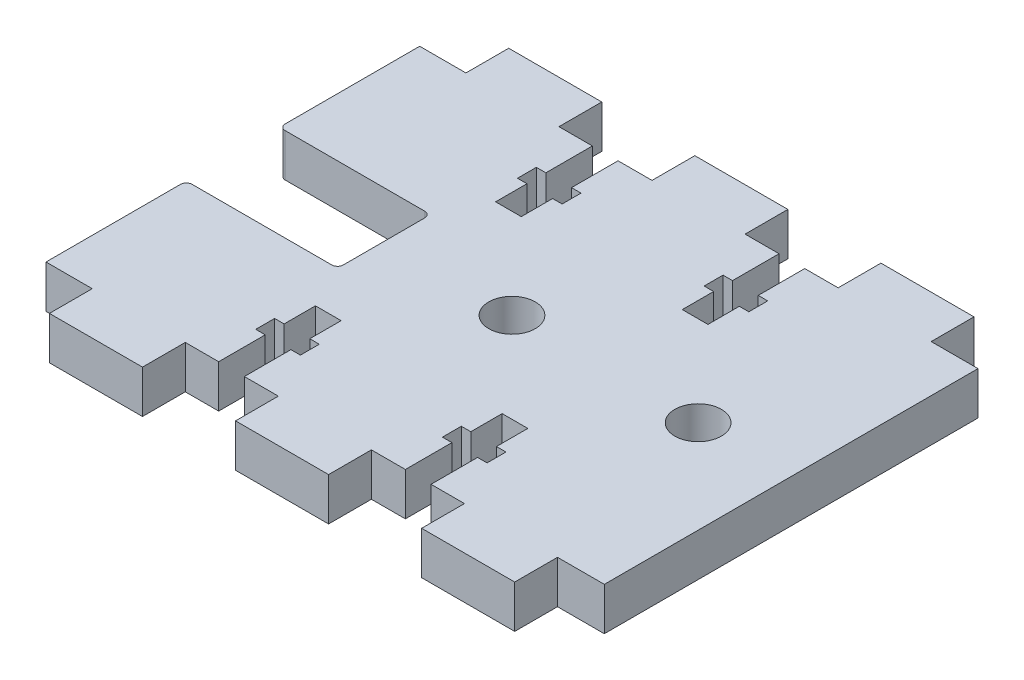
SolidWorks part; units mm, degrees
ref_plane "Front Plane" through (0, 0, 0) normal (0, 0, 1) x (1, 0, 0)
ref_plane "Top Plane" through (0, 0, 0) normal (0, 1, 0) x (1, 0, 0)
ref_plane "Right Plane" through (0, 0, 0) normal (1, 0, 0) x (0, 0, -1)
sketch "Sketch1" plane through (0, 0, 0) normal (0, 1, 0) x (1, 0, 0)
  line L0 (38.1, 0) -> (-38.1, 0) construction
  line L1 (38.1, -25.5) -> (31.7104, -25.5)
  line L2 (38.1, -25.5) -> (38.1, 25.5)
  line L3 (38.1, 25.5) -> (31.7104, 25.5)
  line L4 (-38.1, -25.5) -> (-38.1, 25.5)
  line L5 (38.1, -25.5) -> (-38.1, 25.5) construction
  line L6 (38.1, 25.5) -> (-38.1, -25.5) construction
  line L7 (-0.0396, 25.3) -> (-0.0396, -25.7) construction
  line L8 (-6.3896, 25.5) -> (-11.0266, 25.5)
  line L9 (6.3104, 31.342) -> (-6.3896, 31.342)
  line L10 (6.3104, 31.342) -> (6.3104, 25.5)
  line L11 (-31.7896, 25.5) -> (-38.1, 25.5)
  line L12 (-6.3896, 31.342) -> (-6.3896, 25.5)
  line L13 (6.3104, 31.342) -> (-6.3896, 25.5) construction
  line L14 (6.3104, 25.5) -> (-6.3896, 31.342) construction
  line L15 (31.7104, 31.342) -> (19.0104, 25.5) construction
  line L16 (-31.7896, 25.5) -> (-31.7896, 31.342)
  line L17 (-31.7896, 31.342) -> (-19.0896, 31.342)
  line L18 (-19.0896, 25.5) -> (-19.0896, 31.342)
  line L19 (-31.7896, 25.5) -> (-19.0896, 31.342) construction
  line L20 (-31.7896, 31.342) -> (-19.0896, 25.5) construction
  line L21 (31.7104, 25.5) -> (19.0104, 31.342) construction
  line L22 (19.0104, 25.5) -> (19.0104, 31.342)
  line L23 (31.7104, 31.342) -> (19.0104, 31.342)
  line L24 (31.7104, 25.5) -> (31.7104, 31.342)
  line L25 (19.0104, 25.5) -> (14.4526, 25.5)
  line L26 (-12.7792, 25.1) -> (-12.7792, 0) construction
  line L27 (12.7, 25.5) -> (12.7, -25.5) construction
  line L28 (-9.7312, 16.5719) -> (-9.7312, 19.15)
  line L29 (-14.5318, 16.5719) -> (-15.8272, 16.5719)
  line L30 (-11.0266, 19.15) -> (-11.0266, 25.5)
  line L31 (10.9474, 16.5719) -> (14.4526, 12.292) construction
  line L32 (-14.5318, 19.15) -> (-14.5318, 25.5)
  line L33 (-11.0266, 19.15) -> (-14.5318, 25.5) construction
  line L34 (-11.0266, 25.5) -> (-14.5318, 19.15) construction
  line L35 (-9.7312, 16.5719) -> (-11.0266, 16.5719)
  line L36 (-15.8272, 16.5719) -> (-15.8272, 19.15)
  line L37 (-9.7312, 19.15) -> (-11.0266, 19.15)
  line L38 (-14.5318, 19.15) -> (-15.8272, 19.15)
  line L39 (-14.5318, 25.5) -> (-19.0896, 25.5)
  line L40 (10.9474, 12.292) -> (14.4526, 16.5719) construction
  line L41 (-11.0266, 12.292) -> (-14.5318, 12.292)
  line L42 (-11.0266, 12.292) -> (-11.0266, 16.5719)
  line L43 (10.9474, 25.5) -> (14.4526, 19.15) construction
  line L44 (-14.5318, 12.292) -> (-14.5318, 16.5719)
  line L45 (-11.0266, 12.292) -> (-14.5318, 16.5719) construction
  line L46 (-11.0266, 16.5719) -> (-14.5318, 12.292) construction
  line L47 (10.9474, 19.15) -> (14.4526, 25.5) construction
  line L48 (14.4526, 12.292) -> (14.4526, 16.5719)
  line L49 (10.9474, 12.292) -> (10.9474, 16.5719)
  line L50 (10.9474, 12.292) -> (14.4526, 12.292)
  line L51 (14.4526, 19.15) -> (15.748, 19.15)
  line L52 (9.652, 19.15) -> (10.9474, 19.15)
  line L53 (15.748, 16.5719) -> (15.748, 19.15)
  line L54 (9.652, 16.5719) -> (10.9474, 16.5719)
  line L55 (14.4526, 19.15) -> (14.4526, 25.5)
  line L56 (10.9474, 19.15) -> (10.9474, 25.5)
  line L57 (14.4526, 16.5719) -> (15.748, 16.5719)
  line L58 (9.652, 16.5719) -> (9.652, 19.15)
  line L59 (10.9474, 25.5) -> (6.3104, 25.5)
  line L60 (10.9474, -19.15) -> (14.4526, -25.5) construction
  line L61 (10.9474, -25.5) -> (14.4526, -19.15) construction
  line L62 (10.9474, -12.292) -> (14.4526, -16.5719) construction
  line L63 (10.9474, -16.5719) -> (14.4526, -12.292) construction
  line L64 (9.652, -16.5719) -> (9.652, -19.15)
  line L65 (14.4526, -16.5719) -> (15.748, -16.5719)
  line L66 (10.9474, -19.15) -> (10.9474, -25.5)
  line L67 (14.4526, -19.15) -> (14.4526, -25.5)
  line L68 (9.652, -16.5719) -> (10.9474, -16.5719)
  line L69 (15.748, -16.5719) -> (15.748, -19.15)
  line L70 (9.652, -19.15) -> (10.9474, -19.15)
  line L71 (14.4526, -19.15) -> (15.748, -19.15)
  line L72 (10.9474, -12.292) -> (14.4526, -12.292)
  line L73 (10.9474, -12.292) -> (10.9474, -16.5719)
  line L74 (14.4526, -12.292) -> (14.4526, -16.5719)
  line L75 (-14.5318, -16.5719) -> (-15.8272, -16.5719)
  line L76 (-14.5318, -19.15) -> (-15.8272, -19.15)
  line L77 (-15.8272, -16.5719) -> (-15.8272, -19.15)
  line L78 (-11.0266, -16.5719) -> (-14.5318, -12.292) construction
  line L79 (-11.0266, -12.292) -> (-14.5318, -16.5719) construction
  line L80 (-11.0266, -25.5) -> (-14.5318, -19.15) construction
  line L81 (-11.0266, -19.15) -> (-14.5318, -25.5) construction
  line L82 (-14.5318, -12.292) -> (-14.5318, -16.5719)
  line L83 (-11.0266, -12.292) -> (-11.0266, -16.5719)
  line L84 (-11.0266, -12.292) -> (-14.5318, -12.292)
  line L85 (-9.7312, -19.15) -> (-11.0266, -19.15)
  line L86 (-9.7312, -16.5719) -> (-11.0266, -16.5719)
  line L87 (-14.5318, -19.15) -> (-14.5318, -25.5)
  line L88 (-11.0266, -19.15) -> (-11.0266, -25.5)
  line L89 (-9.7312, -16.5719) -> (-9.7312, -19.15)
  line L90 (-14.5318, -25.5) -> (-19.0896, -25.5)
  line L91 (10.9474, -25.5) -> (6.3104, -25.5)
  line L92 (-31.7896, -25.5) -> (-31.7896, -31.342)
  line L93 (-19.0896, -25.5) -> (-19.0896, -31.342)
  line L94 (-6.3896, -31.342) -> (-6.3896, -25.5)
  line L95 (6.3104, -31.342) -> (6.3104, -25.5)
  line L96 (19.0104, -25.5) -> (19.0104, -31.342)
  line L97 (31.7104, -25.5) -> (31.7104, -31.342)
  line L98 (31.7104, -31.342) -> (19.0104, -31.342)
  line L99 (-31.7896, -31.342) -> (-19.0896, -31.342)
  line L100 (6.3104, -31.342) -> (-6.3896, -31.342)
  line L101 (-31.7896, -25.5) -> (-38.1, -25.5)
  line L102 (-6.3896, -25.5) -> (-11.0266, -25.5)
  line L103 (19.0104, -25.5) -> (14.4526, -25.5)
  line L104 (-15.8272, 17.8609) -> (-9.7312, 17.8609) construction
  point P0 (0, 0)
  point P10 (-0.0396, 28.421)
  point P15 (-25.4396, 28.421)
  point P24 (25.3604, 28.421)
  point P29 (-12.7792, 22.325)
  point P34 (-12.7792, 12.55)
  point P39 (-12.7792, 14.4319)
  point P56 (12.7, 14.4319)
  point P57 (12.7, 12.55)
  point P58 (12.7, 22.325)
  point P68 (12.7, 0)
  point P72 (12.7, -22.325)
  point P73 (12.7, -12.55)
  point P74 (12.7, -14.4319)
  point P87 (-12.7792, -14.4319)
  point P88 (-12.7792, -12.55)
  point P89 (-12.7792, -22.325)
  point P102 (25.3604, -28.421)
  point P103 (-25.4396, -28.421)
  point P104 (-0.0396, -28.421)
  point P107 (-12.7792, 17.8609)
  dimension "D1" = 76.2
  dimension "D2" = 51
  dimension "D3" = 12.7
  dimension "D4" = 5.842
  dimension "D5" = 12.7
  dimension "D6" = 5.842
  dimension "D7" = 25.4
  dimension "D8" = 3.5052
  dimension "D9" = 6.35
  dimension "D10" = 6.096
  dimension "D11" = 2.5781
  dimension "D12" = 4.2799
extrude "Boss-Extrude1" add sketch "Sketch1" along normal blind 5.842
sketch "Sketch2" plane through (0, 5.842, 0) normal (0, 1, 0) x (1, 0, 0)
  line L0 (-38.1, 0) -> (38.1, 0) construction
  line L1 (-38.1, 25.5) -> (-38.1, -25.5) construction
  line L2 (38.1, -25.5) -> (38.1, 25.5) construction
  line L3 (-0.0396, 31.342) -> (-0.0396, -31.342) construction
  line L4 (6.3104, 31.342) -> (-6.3896, 31.342) construction
  line L5 (-6.3896, -31.342) -> (6.3104, -31.342) construction
  circle A0 centre (0, 0) radius 3.175
  circle A1 centre (25.4, 0) radius 3.175
  circle A2 centre (-25.4792, 0) radius 3.175
  dimension "D1" = 6.35
  dimension "D2" = 6.35
  dimension "D3" = 25.4
extrude "Cut-Extrude1" cut sketch "Sketch2" against normal through all
sketch "Sketch3" plane through (0, 5.842, 0) normal (0, 1, 0) x (1, 0, 0)
  line L0 (-38.1, 0) -> (38.1, 0) construction
  line L1 (-38.1, 25.5) -> (-38.1, -25.5) construction
  line L2 (38.1, -25.5) -> (38.1, 25.5) construction
  line L4 (-17.4625, -6.35) -> (-42.8625, -6.35)
  line L5 (-17.4625, -6.35) -> (-17.4625, 6.35)
  line L6 (-17.4625, 6.35) -> (-42.8625, 6.35)
  line L7 (-42.8625, -6.35) -> (-42.8625, 6.35)
  line L8 (-17.4625, -6.35) -> (-42.8625, 6.35) construction
  line L9 (-17.4625, 6.35) -> (-42.8625, -6.35) construction
  point P6 (-30.1625, 0)
  dimension "D1" = 12.7
  dimension "D2" = 25.4
  dimension "D3" = 7.9375
extrude "Cut-Extrude2" cut sketch "Sketch3" against normal through all
fillet "Fillet1" radius 0.7937 4 edges at (-38.1, 2.921, -6.35) (-38.1, 2.921, 6.35) (-17.4625, 2.921, 6.35) (-17.4625, 2.921, -6.35)
